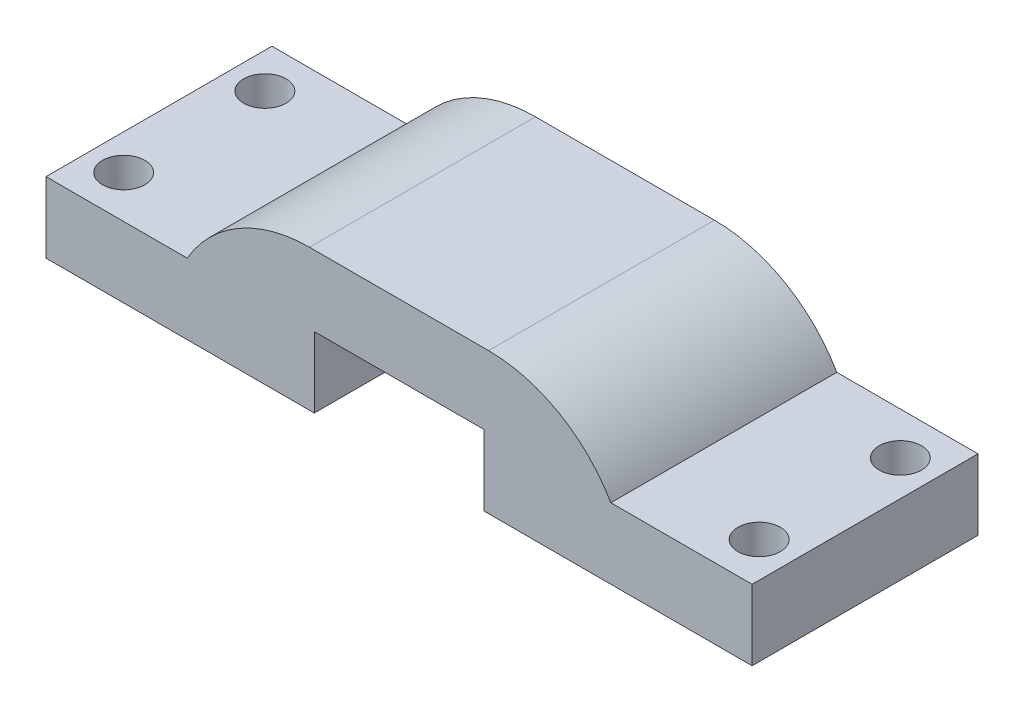
SolidWorks part; units mm, degrees
ref_plane "Front Plane" through (0, 0, 0) normal (0, 0, 1) x (1, 0, 0)
ref_plane "Top Plane" through (0, 0, 0) normal (0, 1, 0) x (1, 0, 0)
ref_plane "Right Plane" through (0, 0, 0) normal (1, 0, 0) x (0, 0, -1)
sketch "Sketch7" plane through (0, 0, 0) normal (0, 0, 1) x (1, 0, 0)
  line L17 (28.8688, -27.166) -> (28.8688, -22.166)
  line L20 (-21.1312, -22.166) -> (-21.1312, -27.166)
  line L24 (-21.1312, -27.166) -> (-8.1312, -27.166)
  line L25 (15.8688, -27.166) -> (28.8688, -27.166)
  line L28 (-11.1312, -22.166) -> (-21.1312, -22.166)
  line L29 (18.8688, -22.166) -> (28.8688, -22.166)
  line L30 (18.8688, -22.166) -> (18.8688, -17.166)
  line L31 (-8.1312, -27.166) -> (-2.1312, -27.166)
  line L32 (3.8688, -27.166) -> (3.8688, -22.166)
  line L37 (9.8688, -27.166) -> (9.8688, -22.166)
  line L38 (-2.1312, -27.166) -> (-2.1312, -22.166)
  line L39 (-2.1312, -22.166) -> (9.8688, -22.166)
  line L40 (18.8688, -17.166) -> (-11.1312, -17.166)
  line L42 (-11.1312, -22.166) -> (-11.1312, -17.166)
  line L45 (9.8688, -27.166) -> (15.8688, -27.166)
  dimension "D3" = 13
  dimension "D4" = 50
  dimension "D10" = 10
  dimension "D11" = 10
  dimension "D2" = 5
  dimension "D9" = 5
  dimension "D1" = 13
  dimension "D5" = 6
  dimension "D6" = 6
  dimension "D7" = 5
  dimension "D8" = 5
extrude "Boss-Extrude1" add sketch "Sketch7" along normal blind 16 contours L37 L45 L25 L17 L29 L30 L40 L42 L28 L20 L24 L31 L38 L39 region at (22.3688, -26.6561, 0)
sketch "Sketch14" plane through (0, -27.166, 0) normal (0, 1, 0) x (1, 0, 0)
  line L0 (18.8688, -16) -> (28.8688, -16) construction
  line L1 (18.8688, 0) -> (28.8688, 0) construction
  line L2 (-11.1312, 0) -> (-21.1312, 0) construction
  line L3 (-11.1312, -16) -> (-21.1312, -16) construction
  line L8 (28.8688, -16) -> (28.8688, 0) construction
  line L12 (-21.1312, -16) -> (-21.1312, 0) construction
  circle A0 centre (-18.6312, -3) radius 1.5
  circle A1 centre (-18.6312, -13) radius 1.5
  circle A2 centre (26.3688, -3) radius 1.5
  circle A3 centre (26.3688, -13) radius 1.5
  dimension "D1" = 2.5
  dimension "D2" = 3
  dimension "D3" = 3
  dimension "D4" = 2.5
  dimension "D5" = 3
  dimension "D6" = 2.5
  dimension "D7" = 2.5
  dimension "D8" = 3
extrude "Cut-Extrude13" cut sketch "Sketch14" along normal blind 50
fillet "Fillet1" radius 10 2 edges at (-11.1312, -17.166, 8) (18.8688, -17.166, 8)
